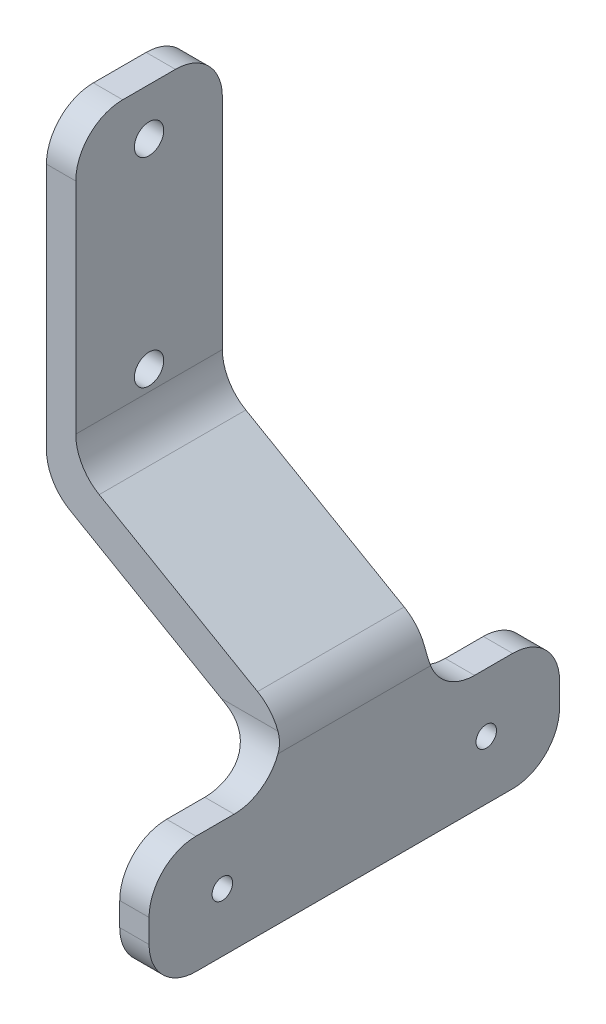
SolidWorks part; units mm, degrees
ref_plane "Front Plane" through (0, 0, 0) normal (0, 0, 1) x (1, 0, 0)
ref_plane "Top Plane" through (0, 0, 0) normal (0, 1, 0) x (1, 0, 0)
ref_plane "Right Plane" through (0, 0, 0) normal (1, 0, 0) x (0, 0, -1)
sketch "Sketch1" plane through (0, 0, 0) normal (0, 0, 1) x (1, 0, 0)
  line L0 (0, 0) -> (0, 25)
  line L1 (0, 25) -> (30, 25)
  line L2 (30, 25) -> (30, 0)
  line L3 (30, 0) -> (0, 0)
  dimension "D1" = 30
  dimension "D2" = 25
extrude "Boss-Extrude1" add sketch "Sketch1" along normal mid plane 25
sketch "Sketch2" plane through (30, 0, 0) normal (1, 0, 0) x (0, 0, -1)
  line L1 (-35, -25) -> (35, -25)
  line L2 (-35, -25) -> (-35, -5)
  line L3 (-35, -5) -> (35, -5)
  line L4 (35, -25) -> (35, -5)
  line L5 (-35, -25) -> (35, -5) construction
  line L6 (-35, -5) -> (35, -25) construction
  line L7 (12.5, 0) -> (12.5, 25) construction
  line L8 (-12.5, 25) -> (12.5, 25) construction
  line L9 (-12.5, 0) -> (12.5, 0) construction
  line L11 (-12.5, 25) -> (12.5, 25)
  line L12 (-12.5, 25) -> (-12.5, -5)
  line L13 (-12.5, -5) -> (12.5, -5)
  line L14 (12.5, 25) -> (12.5, -5)
  point P0 (0, -15)
  point P10 (0, 25)
  line M5 (12.5, 0) -> (12.5, 25)
  line M6 (12.5, 25) -> (-12.5, 25)
  line M7 (-12.5, 25) -> (-12.5, 0)
  line M8 (-12.5, 0) -> (12.5, 0)
  dimension "D1" = 70
  dimension "D2" = 20
  dimension "D3" = 5
extrude "Boss-Extrude2" add sketch "Sketch2" along normal blind 5 contours M8 M5 M6 M7 | L14 L12 L3 M8 | L1 L4 L3 L2
sketch "Sketch5" plane through (0, 0, 0) normal (-1, 0, 0) x (0, 0, 1)
  line L0 (12.5, 25) -> (12.5, 0) construction
  line L1 (-12.5, 0) -> (12.5, 0)
  line L2 (-12.5, 0) -> (-12.5, 75)
  line L3 (-12.5, 75) -> (12.5, 75)
  line L4 (12.5, 0) -> (12.5, 75)
  dimension "D1" = 75
extrude "Boss-Extrude4" add sketch "Sketch5" along normal blind 5 contours L2 L1 L4 L3
sketch "Sketch6" plane through (35, 0, 0) normal (1, 0, 0) x (0, 0, -1)
  line L0 (-22.5, -15) -> (22.5, -15) construction
  line L1 (-35, -25) -> (-35, -5) construction
  circle A0 centre (-22.5, -15) radius 1.75
  circle A1 centre (22.5, -15) radius 1.75
  point P4 (0, -15)
  point P8 (-35, -15)
  dimension "D1" = 3.5
  dimension "D2" = 45
extrude "Cut-Extrude1" cut sketch "Sketch6" against normal through all
sketch "Sketch7" plane through (0, 0, 0) normal (1, 0, 0) x (0, 0, -1)
  line L0 (12.5, 75) -> (-12.5, 75) construction
  line L1 (12.5, 25) -> (-12.5, 25) construction
  circle A0 centre (0, 67) radius 2.5
  circle A1 centre (0, 33) radius 2.5
  point P7 (0, 75)
  dimension "D1" = 5
  dimension "D2" = 8
  dimension "D3" = 8
extrude "Cut-Extrude2" cut sketch "Sketch7" against normal through all
chamfer "Chamfer1" distance 35 angle 30 2 edges at (-5, 0, 0) (35, 25, 0) first distance on face at (12.5, 0, 0) first distance on face at (17.5, 25, 0)
fillet "Fillet1" radius 8 10 edges at (32.5, -25, 35) (32.5, -5, 35) (32.5, -25, -35) (32.5, -5, -35) (30, 0, 0) (35, 4.7927, 0) (-5, 20.2073, 0) (0, 25, 0) (-2.5, 75, 12.5) (-2.5, 75, -12.5)
fillet "Fillet2" radius 8 2 edges at (32.5, -5, -12.5) (32.5, -5, 12.5)
